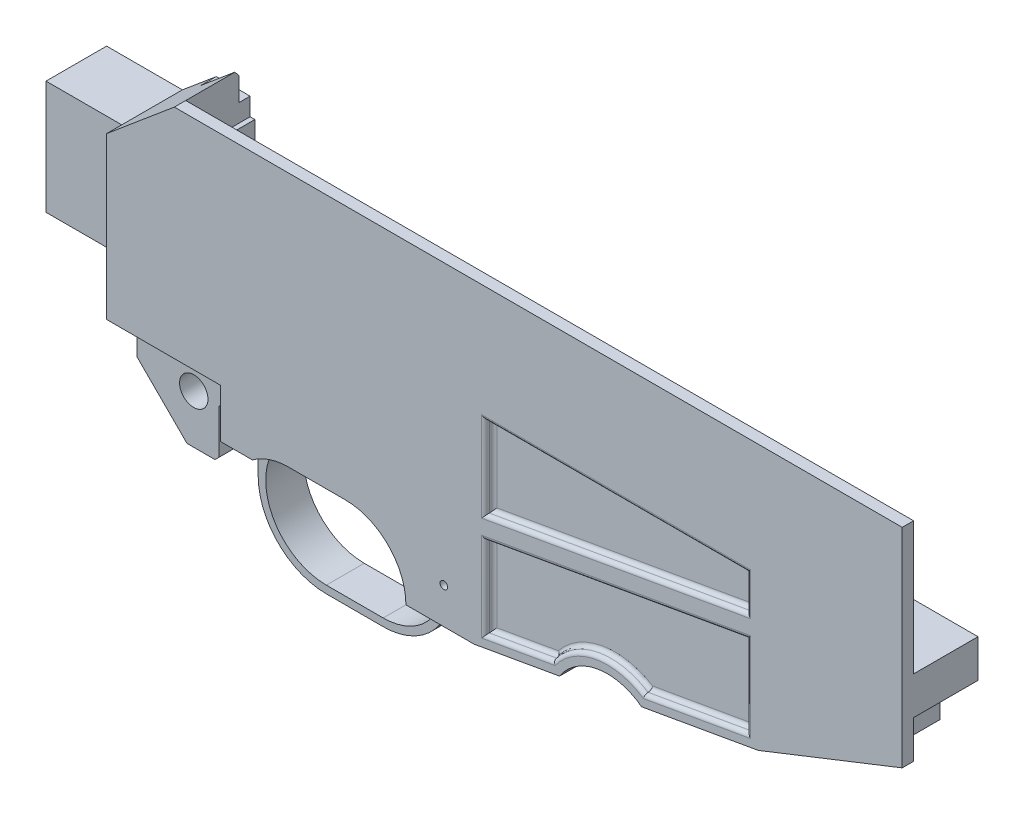
SolidWorks part; units mm, degrees
ref_plane "정면" through (0, 0, 0) normal (0, 0, 1) x (1, 0, 0)
ref_plane "윗면" through (0, 0, 0) normal (0, 1, 0) x (1, 0, 0)
ref_plane "우측면" through (0, 0, 0) normal (1, 0, 0) x (0, 0, -1)
sketch "스케치2" plane through (0, 0, 0) normal (0, 0, 1) x (1, 0, 0)
  line L0 (0, 0) -> (20, 0)
  line L1 (20, 0) -> (37.8763, 15)
  line L2 (37.8763, 15) -> (230, 15)
  line L3 (230, 15) -> (230, -54.9955)
  line L4 (230, -54.9955) -> (192, -54.9955)
  line L5 (117, -68.22) -> (101, -68.22)
  line L6 (0, 0) -> (0, -30)
  line L7 (0, -30) -> (20, -30)
  line L8 (20, -30) -> (20, -55)
  line L9 (20, -55) -> (33.22, -68.22)
  line L10 (33.22, -68.22) -> (50, -68.22)
  line L11 (117, -68.22) -> (139.5521, -64.2435)
  line L12 (68, -68.22) -> (83, -68.22) construction
  line L13 (68, -52.22) -> (83, -52.22)
  line L14 (68, -84.22) -> (83, -84.22)
  line L15 (161.2179, -60.4232) -> (192, -54.9955)
  line L16 (68, -86.22) -> (83, -86.22)
  line L17 (71.3269, -49.22) -> (86.3269, -49.22)
  line L19 (68, -50.22) -> (83, -50.22) construction
  arc A0 (68, -52.22) -> (68, -84.22) centre (68, -68.22) ccw
  arc A1 (83, -84.22) -> (83, -52.22) centre (83, -68.22) ccw
  arc A2 (83, -86.22) -> (101, -68.22) centre (83, -68.22) ccw
  arc A3 (50, -68.22) -> (68, -86.22) centre (68, -68.22) ccw
  arc A5 (139.5521, -64.2435) -> (161.2179, -60.4232) centre (152.1559, -72.3764) cw
  arc A6 (68, -50.22) -> (68, -86.22) centre (68, -68.22) ccw construction
  arc A7 (83, -86.22) -> (83, -50.22) centre (83, -68.22) ccw construction
  point P16 (75.5, -68.22)
  point P27 (50, -68.22)
  point P30 (101, -68.22)
  point P34 (139.5521, -64.2435)
  point P35 (161.2179, -60.4232)
  dimension "D11" = 16
  dimension "D15" = 22
  dimension "D16" = 15
  dimension "D1" = 230
  dimension "D2" = 30
  dimension "D3" = 30
  dimension "D4" = 135
  dimension "D5" = 140
  dimension "D6" = 15
  dimension "D7" = 75
  dimension "D8" = 16
  dimension "D9" = 15
  dimension "D12" = 3
  dimension "D13" = 64.22
  dimension "D14" = 170
  dimension "D17" = 20
  dimension "D18" = 25
  dimension "D19" = 16
  dimension "D20" = 22.9
  dimension "D21" = 20
  dimension "D10" = 2
extrude "보스-돌출1" add sketch "스케치2" along normal blind 20 contours A5 L15 L4 L3 L2 L1 L0 L6 L7 L8 L9 L10 A3 L16 A2 L5 A1 L14 A0 L13 region at (119.6066, -23.0148, 0)
sketch "스케치3" plane through (0, 0, 0) normal (0, 0, -1) x (-1, 0, 0)
  line L0 (-68, -52.22) -> (-83, -52.22) construction
  line L1 (-39.125, -49.22) -> (-111.875, -49.22)
  line L2 (-39.125, -49.22) -> (-39.125, 2.78)
  line L3 (-39.125, 2.78) -> (-111.875, 2.78)
  line L4 (-111.875, -49.22) -> (-111.875, 2.78)
  line L5 (-75.5, -52.22) -> (-75.5, -49.22) construction
  point P6 (-75.5, -52.22)
  point P9 (-75.5, -49.22)
  dimension "D1" = 52
  dimension "D2" = 72.75
  dimension "D3" = 3
extrude "컷-돌출1" cut sketch "스케치3" against normal blind 8
sketch "스케치4" plane through (0, 0, 0) normal (0, 0, -1) x (-1, 0, 0)
  line L1 (-37.8763, 2.78) -> (-211, 2.78)
  line L3 (-37.8763, 15) -> (-211, 15)
  line L4 (-211, 2.78) -> (-211, 15)
  line L5 (-37.8763, 2.78) -> (-37.8763, 15)
  line L6 (-211, -54.9955) -> (-211, 15) construction
  line L7 (-230, -54.9955) -> (-192, -54.9955) construction
  line L8 (-37.8763, 15) -> (-230, 15) construction
  dimension "D2" = 12.22
extrude "컷-돌출2" cut sketch "스케치4" against normal blind 17
sketch "스케치5" plane through (0, 0, 0) normal (0, 0, -1) x (-1, 0, 0)
  line L0 (-117, -68.22) -> (-117, 2.78)
  line L1 (-117, 2.78) -> (-192, 2.78)
  line L2 (-192, 2.78) -> (-192, -54.9955)
  line L3 (-211, 2.78) -> (-37.8763, 2.78) construction
  line L5 (-192, -54.9955) -> (-161.2179, -60.4232)
  line L6 (-139.5521, -64.2435) -> (-117, -68.22)
  line L7 (-117, -68.22) -> (-120.7282, -69.1071)
  arc A0 (-161.2179, -60.4232) -> (-139.5521, -64.2435) centre (-152.1559, -72.3764) cw
  line M11 (-192, -54.9955) -> (-161.2179, -60.4232)
  arc M12 (-161.2179, -60.4232) -> (-139.5521, -64.2435) centre (-152.1559, -72.3764) cw
  line M13 (-139.5521, -64.2435) -> (-117, -68.22)
extrude "컷-돌출3" cut sketch "스케치5" against normal blind 14 contours L1 L2 L0 M11 M12 M13 region at (153.265, -29.0527, 0)
sketch "스케치6" plane through (0, 0, 0) normal (0, 0, -1) x (-1, 0, 0)
  line L1 (-111.875, -49.22) -> (-39.125, -49.22) construction
  line L2 (-88, -49.22) -> (-63, -49.22)
  line L3 (-83, -52.22) -> (-68, -52.22)
  line L4 (-88, -49.22) -> (-88, -53.0213)
  line L6 (-63, -49.22) -> (-63, -53.0213)
  arc A2 (-68, -84.22) -> (-68, -52.22) centre (-68, -68.22) ccw construction
  arc A3 (-83, -52.22) -> (-83, -84.22) centre (-83, -68.22) ccw construction
  arc A4 (-63, -53.0213) -> (-68, -52.22) centre (-68, -68.22) ccw
  arc A5 (-83, -52.22) -> (-88, -53.0213) centre (-83, -68.22) ccw
  point P0 (-75.5, -49.22)
  dimension "D1" = 25
extrude "컷-돌출4" cut sketch "스케치6" against normal blind 5
sketch "스케치7" plane through (0, 0, 20) normal (0, 0, 1) x (1, 0, 0)
  line L0 (20, -42.5) -> (50, -42.5)
  line L1 (20, -30) -> (20, -55) construction
  line L2 (50, -42.5) -> (50, -68.22)
  line L3 (50, -68.22) -> (33.22, -68.22)
  line L4 (33.22, -68.22) -> (20, -55)
  line L5 (20, -55) -> (20, -42.5)
extrude "컷-돌출5" cut sketch "스케치7" against normal blind 8
sketch "스케치8" plane through (0, 0, 12) normal (0, 0, 1) x (1, 0, 0)
  line L0 (41.61, -68.22) -> (50, -68.22)
  line L1 (33.22, -68.22) -> (50, -68.22) construction
  line L2 (50, -68.22) -> (50, -55.36)
  line L3 (50, -68.22) -> (50, -42.5) construction
  line L4 (50, -55.36) -> (41.61, -55.36)
  line L5 (41.61, -55.36) -> (41.61, -68.22)
sketch "스케치9" plane through (0, -86.22, 0) normal (0, -1, 0) x (1, 0, 0)
  line L0 (75.5, 20) -> (50, 20)
  line L1 (68, 20) -> (83, 20) construction
  line L2 (50, 20) -> (50, 10)
  line L3 (50, 10) -> (101, 10)
  line L4 (101, 20) -> (101, 0) construction
  line L5 (101, 10) -> (101, 20)
  line L6 (101, 20) -> (75.5, 20)
  line L7 (75.5, 20) -> (75.5, 10)
  line M3 (83, 0) -> (83, 20)
  line M4 (83, 20) -> (68, 20)
  line M5 (68, 20) -> (68, 0)
  dimension "D1" = 10
extrude "컷-돌출7" cut sketch "스케치9" against normal up to surface (18 mm away) contours L5 L6 L3 M3 | L7 L3 M4 M3 region at (79.25, -86.22, 15) region at (92, -86.22, 15) up to face at (110.6, -68.22, 10.8)
extrude "컷-돌출9" cut sketch "스케치9<4>" against normal up to vertex (30.86 mm away) contours L7 L3 M4 M5 | L2 L3 L0 M5 region at (71.75, -86.22, 15) region at (59, -86.22, 15) up to point (50, -55.36, 12)
sketch "스케치9<4>" plane through (0, -86.22, 0) normal (0, -1, 0) x (1, 0, 0) same geometry as "스케치9"
fillet "필렛2" radius 7.5 1 edges at (54.2403, -55.36, 10) second distance 9 first distance on face at (72.5955, -74.4968, 10)
extrude "컷-돌출11" cut sketch "스케치8" against normal blind 6 contours L0 L2 L4 L5
chamfer "모따기2" distance 1 angle 45 1 edges at (41.61, -68.22, 9)
fillet "필렛3" radius 6 1 edges at (100, -68.22, 10) second distance 8 first distance on face at (107.2857, -68.22, 10.5714)
sketch "스케치11" plane through (0, 0, 0) normal (0, 0, -1) x (-1, 0, 0)
  line L1 (-230, 15) -> (-111.87, 15)
  line L2 (-230, 15) -> (-230, -20)
  line L3 (-230, -20) -> (-111.87, -20)
  line L4 (-111.87, 15) -> (-111.87, -20)
  dimension "D1" = 35
  dimension "D2" = 118.13
extrude "컷-돌출15" cut sketch "스케치11" against normal blind 17
sketch "스케치12" plane through (0, 0, 0) normal (0, 0, -1) x (-1, 0, 0)
  line L1 (-230, -54.9955) -> (-220, -54.9955)
  line L2 (-230, -54.9955) -> (-230, -29.9955)
  line L3 (-230, -29.9955) -> (-220, -29.9955)
  line L4 (-220, -54.9955) -> (-220, -29.9955)
  dimension "D1" = 10
  dimension "D2" = 25
extrude "컷-돌출16" cut sketch "스케치12" against normal blind 17
sketch "스케치16" plane through (0, 0, 20) normal (0, 0, 1) x (1, 0, 0)
  line L0 (192, -54.9955) -> (230, -39.9955)
  line L1 (230, 15) -> (230, -54.9955) construction
  line L2 (230, -39.9955) -> (230, -54.9955)
  line L3 (230, -54.9955) -> (192, -54.9955)
  dimension "D1" = 15
extrude "컷-돌출18" cut sketch "스케치16" against normal up to next
sketch "스케치17" plane through (0, 0, 20) normal (0, 0, 1) x (1, 0, 0)
  line L0 (37.8763, 15) -> (116.9763, 15) construction
  line L1 (37.8763, 15) -> (230, 15) construction
  line L2 (116.9763, 15) -> (116.9763, 13)
  line L3 (116.9763, 13) -> (190.9763, 13)
  line L4 (190.9763, 13) -> (190.9763, 15)
  line L5 (116.9763, 15) -> (190.9763, 15)
  dimension "D1" = 79.1
  dimension "D2" = 74
  dimension "D3" = 2
sketch "스케치18" plane through (0, 0, 0) normal (0, 0, -1) x (-1, 0, 0)
  line L0 (-101, -68.22) -> (-117, -49.22) construction
  circle A0 centre (-109, -58.72) radius 1.75
  dimension "D1" = 3.5
extrude "컷-돌출20" cut sketch "스케치18" against normal blind 6
sketch "스케치20" plane through (0, 0, 0) normal (0, 0, -1) x (-1, 0, 0)
  line L1 (-117, -68.22) -> (-101, -68.22) construction
  line L2 (-117, -68.22) -> (-117, -20) construction
  line L3 (-113, -68.22) -> (-103, -68.22)
  line L4 (-103, -68.22) -> (-103, -50.22)
  line L5 (-103, -50.22) -> (-111.875, -50.22)
  line L6 (-111.875, -50.22) -> (-111.875, -36.22)
  line L8 (-111.875, -36.22) -> (-117, -36.22)
  line L9 (-117, -36.22) -> (-117, -64.22)
  line L10 (-117, -64.22) -> (-117, -68.22)
  line L11 (-117, -68.22) -> (-113, -68.22)
  dimension "D1" = 4
  dimension "D3" = 10
  dimension "D4" = 18
  dimension "D5" = 14
extrude "컷-돌출21" cut sketch "스케치20" against normal blind 4.25
sketch "스케치21" plane through (0, 0, 6) normal (0, 0, -1) x (-1, 0, 0)
  circle A0 centre (-109, -58.72) radius 1
  dimension "D1" = 2
extrude "컷-돌출22" cut sketch "스케치21" against normal up to next
fillet "필렛5" radius 2 1 edges at (103, -50.22, 2.125)
sketch "스케치22" plane through (0, 0, 12) normal (0, 0, 1) x (1, 0, 0)
  line L0 (20, -42.5) -> (50, -68.22) construction
  circle A0 centre (35, -55.36) radius 3.75
  dimension "D1" = 7.5
extrude "컷-돌출23" cut sketch "스케치22" against normal up to next
chamfer "모따기3" distance 1 angle 45 1 edges at (111.875, -50.22, 2.125)
sketch "스케치23" plane through (117, 0, 0) normal (1, 0, 0) x (0, 0, -1)
  line L0 (-4.5, -33.22) -> (-4.5, -68.22)
  line L2 (-14, -68.22) -> (-4.25, -68.22) construction
  line L3 (0, -36.22) -> (0, -20) construction
  line L4 (-4.5, -33.22) -> (0, -33.22)
  line L5 (0, -33.22) -> (0, -68.22)
  line L6 (0, -68.22) -> (-4.5, -68.22)
  dimension "D1" = 4.5
  dimension "D2" = 35
extrude "컷-돌출24" cut sketch "스케치23" against normal blind 2
sketch "스케치24" plane through (103, 0, 0) normal (1, 0, 0) x (0, 0, -1)
  line L0 (0, -68.22) -> (0, -52.22) construction
  circle A0 centre (0, -53.72) radius 2.5
  dimension "D1" = 5
  dimension "D2" = 14.5
extrude "컷-돌출25" cut sketch "스케치24" against normal mid plane 10
sketch "스케치25" plane through (0, 0, 20) normal (0, 0, 1) x (1, 0, 0)
  line L1 (0, 0) -> (20, 0)
  line L2 (0, 0) -> (0, -30)
  line L3 (0, -30) -> (20, -30)
  line L4 (20, 0) -> (20, -30)
extrude "컷-돌출26" cut sketch "스케치25" against normal blind 4
sketch "스케치30" plane through (0, 0, 20) normal (0, 0, 1) x (1, 0, 0)
  line L0 (117, -68.22) -> (117, 0)
  line L1 (117, 0) -> (192, 0)
  line L2 (192, 0) -> (192, -54.9955)
  line L3 (117, -68.22) -> (139.5521, -64.2435) construction
  line L4 (161.2179, -60.4232) -> (192, -54.9955) construction
  line L5 (117, -68.22) -> (139.5521, -64.2435)
  line L6 (161.2179, -60.4232) -> (192, -54.9955)
  line L7 (120, -64.6447) -> (137.8102, -61.5043)
  line L8 (120, -64.6447) -> (120, -15.7418)
  line L9 (120, -3) -> (174.9862, -3)
  line L10 (189, -3.5753) -> (189, -52.4782)
  line L11 (161.9179, -57.2535) -> (189, -52.4782)
  line L12 (117, -13.2245) -> (192, 0)
  line L13 (120, -15.7418) -> (189, -3.5753)
  line L14 (120, -12.6955) -> (120, -3)
  line L15 (120, -3) -> (189, -3) construction
  line L16 (102.969, -15.6986) -> (201.3298, 1.6451) construction
  line L17 (103.49, -18.653) -> (201.8507, -1.3093) construction
  line L18 (189, -3) -> (189, -52.4782) construction
  line L19 (189, -28.0267) -> (120, -40.1933)
  line L20 (120, -64.6447) -> (120, -3) construction
  line L21 (189, -25.0723) -> (120, -37.2389)
  line L22 (189, -30.9811) -> (120, -43.1477)
  line L23 (120, -15.7418) -> (189, -15.7418)
  arc A0 (161.2179, -60.4232) -> (139.5521, -64.2435) centre (152.1559, -72.3764) ccw construction
  arc A1 (161.2179, -60.4232) -> (139.5521, -64.2435) centre (152.1559, -72.3764) ccw
  arc A2 (161.9179, -57.2535) -> (137.8102, -61.5043) centre (152.1559, -72.3764) ccw
  dimension "D2" = 3
  dimension "D1" = 3
extrude "컷-돌출27" cut sketch "스케치30" against normal blind 2 contours A2 L11 L10 L9 L8 L7 | L23 L8 L21 L10 region at (154.7863, -47.2575, 20) region at (149.9613, -23.8488, 20)
fillet "필렛6" radius 1 20 edges at (128.9051, -63.0745, 20) (128.9051, -63.0745, 18) (149.0302, -54.6499, 20) (149.0302, -54.6499, 18) (175.4589, -54.8658, 18) (175.4589, -54.8658, 20) (189, -41.7297, 20) (120, -53.8962, 20) (120, -53.8962, 18) (189, -41.7297, 18) (154.5, -37.0644, 20) (154.5, -37.0644, 18) (189, -20.4071, 20) (189, -20.4071, 18) (154.5, -31.1556, 20) (154.5, -31.1556, 18) (120, -26.4903, 18) (120, -26.4903, 20) (154.5, -15.7418, 18) (154.5, -15.7418, 20)
sketch "스케치32" plane through (37.8763, 0, 0) normal (1, 0, 0) x (0, 0, -1)
  line L1 (0, 15) -> (-3, 15)
  line L2 (0, 15) -> (0, 7.5)
  line L3 (0, 7.5) -> (-3, 7.5)
  line L4 (-3, 15) -> (-3, 7.5)
  dimension "D1" = 3
  dimension "D2" = 7.5
extrude "컷-돌출28" cut sketch "스케치32" against normal blind 10
chamfer "모따기5" distance 1 angle 45 1 edges at (33.4072, 11.25, 3)
sketch "스케치33" plane through (0, -68.22, 0) normal (0, -1, 0) x (1, 0, 0)
  line L0 (33.22, 0) -> (50, 0) construction
  circle A0 centre (43.375, 0) radius 2
  dimension "D2" = 4
  dimension "D1" = 6.625
extrude "컷-돌출29" cut sketch "스케치33" against normal through all
chamfer "모따기6" distance 1 angle 45 1 edges at (43.375, -68.22, 2)
sketch "스케치34" plane through (0, -49.22, 0) normal (0, 1, 0) x (1, 0, 0)
  line L0 (111.875, 0) -> (88, 0) construction
  line L1 (101.6, 0) -> (97.65, 0)
  circle A0 centre (99.625, 0) radius 1.975
  line M8 (111.875, 0) -> (88, 0)
  dimension "D2" = 3.95
  dimension "D1" = 12.25
extrude "보스-돌출2" add sketch "스케치34" along normal blind 2 contours A0 M8 region at (99.625, -49.22, 0.8382)
chamfer "모따기7" distance 0.5 angle 45 1 edges at (99.625, -47.22, 1.975)
